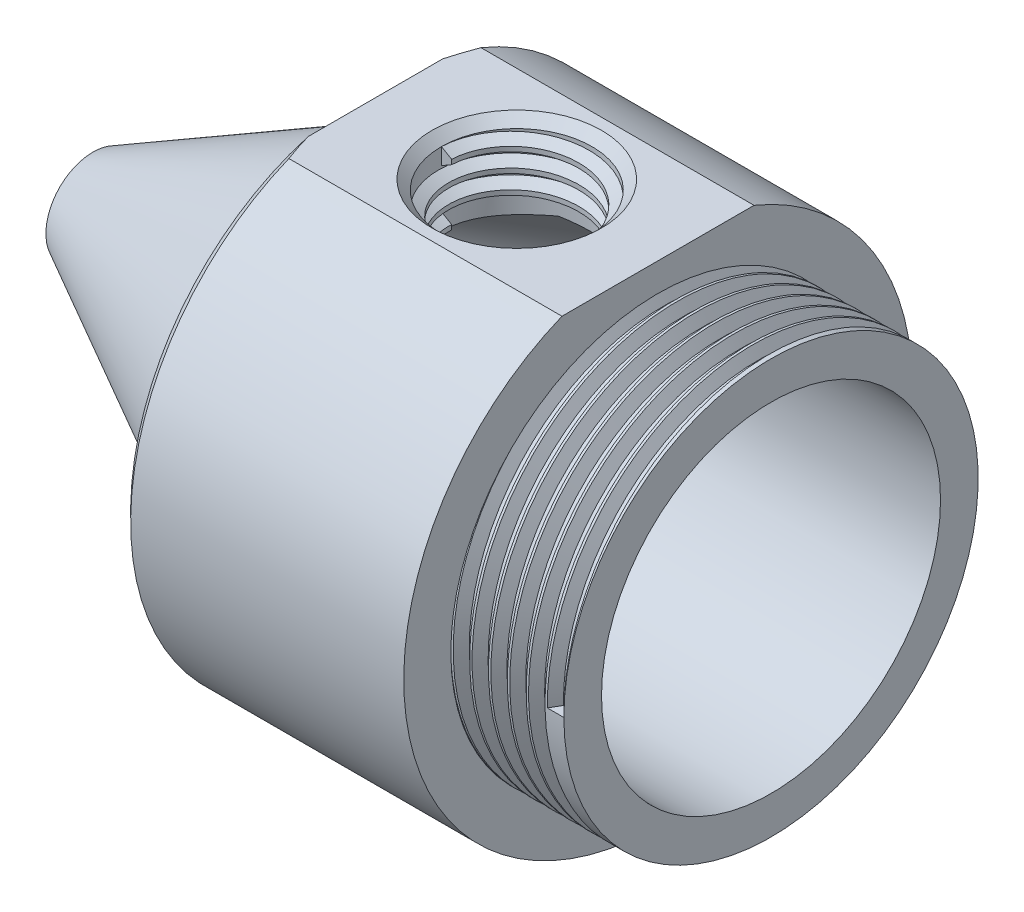
SolidWorks part; units mm, degrees
material "1060 Сплав"
ref_plane "Спереди" through (0, 0, 0) normal (0, 0, 1) x (1, 0, 0)
ref_plane "Сверху" through (0, 0, 0) normal (0, 1, 0) x (1, 0, 0)
ref_plane "Справа" through (0, 0, 0) normal (1, 0, 0) x (0, 0, -1)
sketch "Эскиз1" plane through (0, 0, 0) normal (0, 0, 1) x (1, 0, 0)
  line L0 (15.9231, 8.9551) -> (9.9231, 8.9551)
  line L1 (9.9231, 8.9551) -> (9.9231, 11.4551)
  line L2 (9.9231, 11.4551) -> (-5.0769, 11.4551)
  line L3 (-5.0769, 11.4551) -> (-5.0769, 8.4551)
  line L4 (-5.0769, 8.4551) -> (-20.0769, 0.4551)
  line L5 (-20.0769, 0.4551) -> (-20.0769, -1.0449)
  line L6 (-20.0769, -1.0449) -> (-18.0769, -1.0449)
  line L7 (-18.0769, -1.0449) -> (-11.0375, 2.7095)
  line L8 (-11.0375, 2.7095) -> (0.9231, 6.9551)
  line L9 (0.9231, 6.9551) -> (15.9231, 6.9551)
  line L10 (15.9231, 6.9551) -> (15.9231, 8.9551)
  line L11 (-1022.2821, -2.0449) -> (-20.0769, -2.0449) construction
  line L12 (-18.0769, -2.0449) -> (35.8205, -2.0449) construction
  dimension "D1" = 11
  dimension "D2" = 6
  dimension "D3" = 13.5
  dimension "D4" = 10.5
  dimension "D5" = 2.5
  dimension "D6" = 2
  dimension "D7" = 15
  dimension "D8" = 2
  dimension "D9" = 15
  dimension "D10" = 1
revolve "Повернуть1" add sketch "Эскиз1" angle 360 about L11
thread "Резьба1" pitch 1 method cut profile "Профиль резьбы1" start angle 0, offset 0, length 6, pitch 1, diameter 22
ref_plane "Плоскость1" through (15.9231, -2.0449, 11) normal (0, -1, 0) x (0, 0, 1)
sketch "Профиль резьбы1" plane through (15.9231, -2.0449, 11) normal (0, -1, 0) x (0, 0, 1)
  line L0 (0, 0) -> (0, 1) construction
  line L11 (0, 0) -> (0, 0.875)
  line L12 (0, 0.875) -> (-0.5413, 0.5625)
  line L13 (-0.5413, 0.5625) -> (-0.5413, 0.3125)
  line L15 (-0.5413, 0.3125) -> (0, 0)
  line L17 (-0.5413, 0.4375) -> (0, 0.4375) construction
  point P2 (0, 0)
  dimension "Pitch" = 1
  dimension "Profile_Angle" = 60
  dimension "Profile_Land" = 0.25
  dimension "Profile_Height" = 0.5413
sketch "Эскиз4" plane through (9.9231, 0, 0) normal (1, 0, 0) x (0, 0, -1)
  line L1 (-11, 12.5239) -> (11, 12.5239)
  line L2 (-11, 12.5239) -> (-11, 10.4551)
  line L3 (-11, 10.4551) -> (11, 10.4551)
  line L4 (11, 12.5239) -> (11, 10.4551)
  circle A0 centre (0, -2.0449) radius 13.5 construction
  dimension "D1" = 22
  dimension "D2" = 11
  dimension "D3" = 12.5
extrude "Вырез-Вытянуть1" cut sketch "Эскиз4" against normal up to next
sketch "Эскиз5" plane through (0, 10.4551, 0) normal (0, 1, 0) x (1, 0, 0)
  line L1 (-5.0769, 5.099) -> (-5.0769, -5.099) construction
  line L2 (9.9231, 5.099) -> (-5.0769, 5.099) construction
  circle A0 centre (2.4231, 0) radius 4
  point P6 (-5.0769, 0)
  dimension "D1" = 8
  dimension "D2" = 7.5
  dimension "D3" = 5.099
extrude "Вырез-Вытянуть2" cut sketch "Эскиз5" against normal up to next
chamfer "Фаска1" distance 0.5 angle 45 1 edges at (2.4231, 10.4551, 4)
chamfer "Фаска2" distance 0.5 angle 45 1 edges at (-5.0769, -15.5449, 0)
thread "Резьба4" pitch 1 method extrude profile "Профиль резьбы4" start angle 0, offset 0, length 3, pitch 1, diameter 8
ref_plane "Плоскость4" through (-1.5769, 9.9551, 0) normal (0, 0, 1) x (-1, 0, 0)
sketch "Профиль резьбы4" plane through (-1.5769, 9.9551, 0) normal (0, 0, 1) x (-1, 0, 0)
  line L0 (0, 0) -> (0, 1) construction
  line L11 (0, 0) -> (0, 0.875)
  line L12 (0, 0.875) -> (-0.5413, 0.5625)
  line L13 (-0.5413, 0.5625) -> (-0.5413, 0.3125)
  line L15 (-0.5413, 0.3125) -> (0, 0)
  line L17 (-0.5413, 0.4375) -> (0, 0.4375) construction
  point P2 (0, 0)
  dimension "Pitch" = 1
  dimension "Profile_Angle" = 60
  dimension "Profile_Land" = 0.25
  dimension "Profile_Height" = 0.5413
